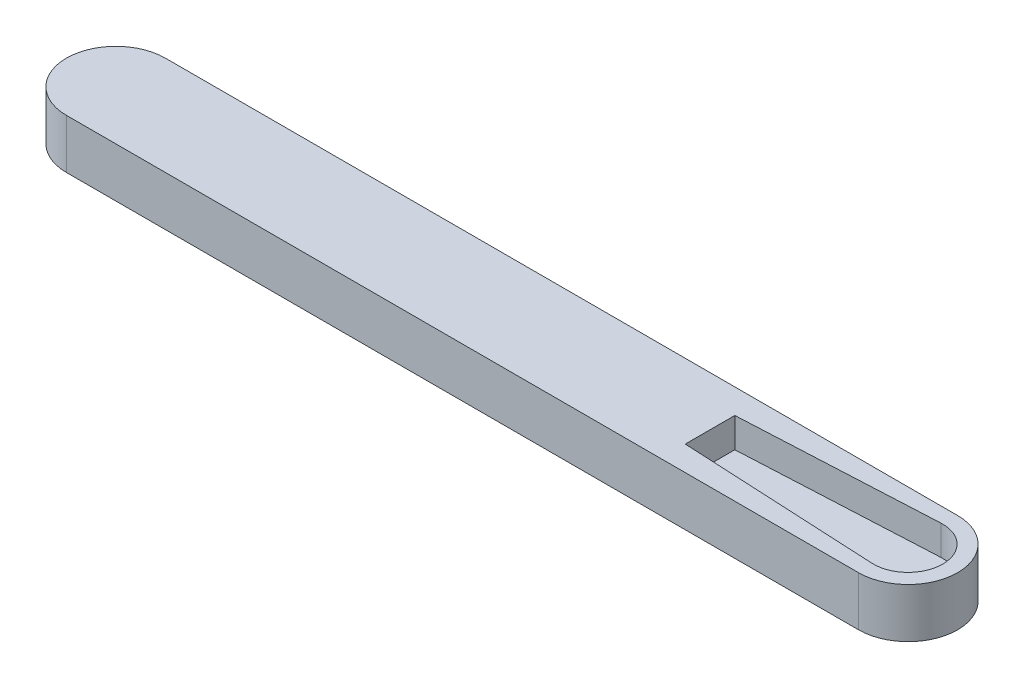
SolidWorks part; units mm, degrees
ref_plane "Ön Düzlem" through (0, 0, 0) normal (0, 0, 1) x (1, 0, 0)
ref_plane "Üst Düzlem" through (0, 0, 0) normal (0, 1, 0) x (1, 0, 0)
ref_plane "Sağ Düzlem" through (0, 0, 0) normal (1, 0, 0) x (0, 0, -1)
sketch "Çizim1" plane through (0, 0, 0) normal (0, 1, 0) x (1, 0, 0)
  line L0 (0, 0) -> (80, 0) construction
  line L1 (0, 5) -> (80, 5)
  line L2 (0, -5) -> (80, -5)
  line L3 (79.8244, 3.4956) -> (60, 2.5)
  line L4 (60, 2.5) -> (60, -2.5)
  line L5 (60, -2.5) -> (79.8244, -3.4956)
  arc A0 (0, 5) -> (0, -5) centre (0, 0) ccw
  arc A1 (80, -5) -> (80, 5) centre (80, 0) ccw
  arc A2 (79.8244, -3.4956) -> (79.8244, 3.4956) centre (80, 0) ccw
  point P3 (40, 0)
  point P14 (0, 0)
  point P15 (0, 0)
  dimension "D1" = 5
  dimension "D3" = 7
  dimension "D2" = 80
  dimension "D4" = 20
  dimension "D5" = 5
extrude "Yükseklik-Ekstrüzyon1" add sketch "Çizim1" along normal blind 5 contours L2 A1 L1 A0 A2 L5 L4 L3 region at (33.9559, 0, 0)
extrude "Yükseklik-Ekstrüzyon2" add sketch "Çizim1<4>" along normal blind 2 contours L5 A2 L3 L4 region at (72.0668, 0, 0)
sketch "Çizim1<4>" plane through (0, 0, 0) normal (0, 1, 0) x (1, 0, 0) same geometry as "Çizim1"
